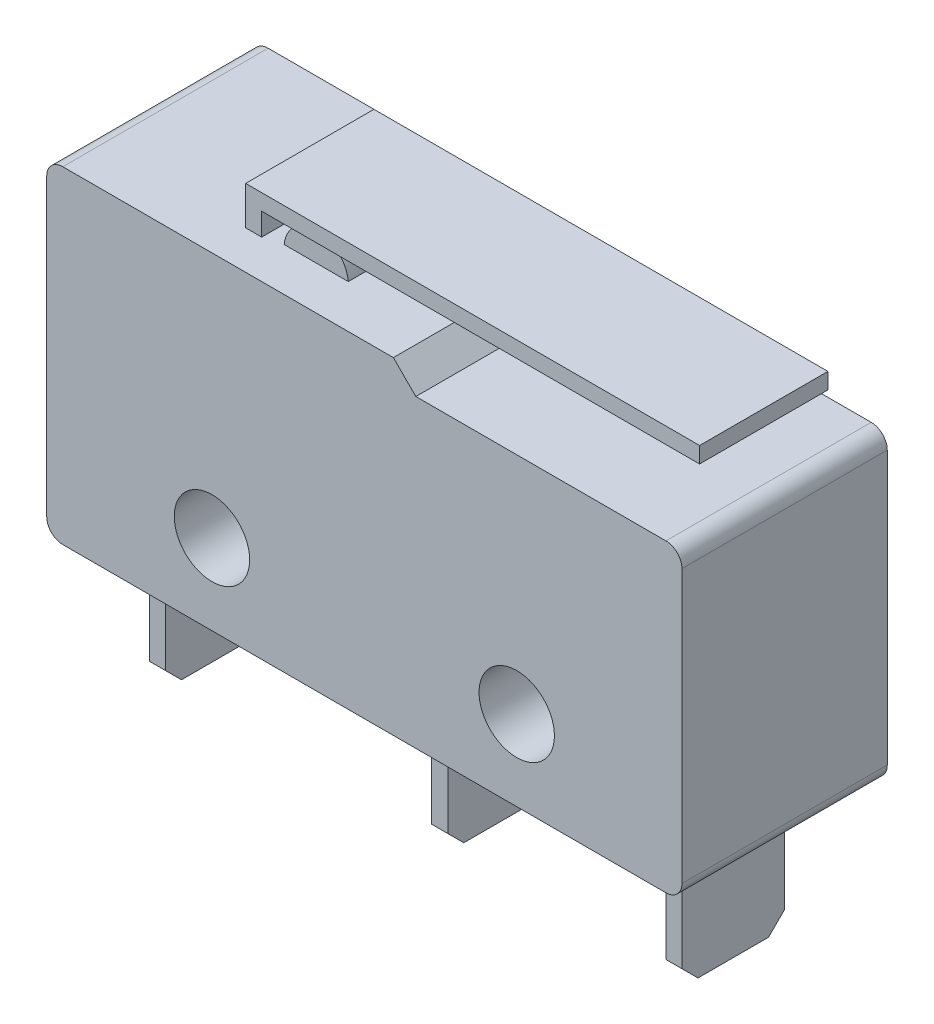
SolidWorks part; units mm, degrees
ref_plane "前视基准面" through (0, 0, 0) normal (0, 0, 1) x (1, 0, 0)
ref_plane "上视基准面" through (0, 0, 0) normal (0, 1, 0) x (1, 0, 0)
ref_plane "右视基准面" through (0, 0, 0) normal (1, 0, 0) x (0, 0, -1)
other "Configuration Table"
sketch "草图1" plane through (0, 0, 0) normal (0, 0, 1) x (1, 0, 0)
  line L1 (9.9, 5.1) -> (-9.9, 5.1)
  line L2 (9.9, 5.1) -> (9.9, -5.1)
  line L3 (9.9, -5.1) -> (-9.9, -5.1)
  line L4 (-9.9, 5.1) -> (-9.9, -5.1)
  line L5 (9.9, 5.1) -> (-9.9, -5.1) construction
  line L6 (9.9, -5.1) -> (-9.9, 5.1) construction
  point P0 (0, 0)
  dimension "D1" = 10.2
  dimension "D2" = 19.8
extrude "凸台-拉伸1" add sketch "草图1" along normal blind 6.4
sketch "草图2" plane through (0, 0, 6.4) normal (0, 0, 1) x (1, 0, 0)
  line L0 (0.0073, 5.998) -> (1.6053, 4.4)
  line L1 (1.6053, 4.4) -> (11.594, 4.4)
  line L2 (11.594, 4.4) -> (11.594, 6.8418)
  line L3 (11.594, 6.8418) -> (0.0073, 6.9858)
  line L4 (0.0073, 6.9858) -> (0.0073, 6.1215)
  line L5 (-9.9, -5.1) -> (9.9, -5.1) construction
  line L6 (9.9, 5.1) -> (-9.9, 5.1) construction
  dimension "D1" = 9.5
  dimension "D2" = 45
extrude "切除-拉伸1" cut sketch "草图2" against normal through all and the other way through all
sketch "草图3" plane through (0, 0, 6.4) normal (0, 0, 1) x (1, 0, 0)
  line L0 (0, 0) -> (0, -5.1) construction
  line L1 (-9.9, -5.1) -> (9.9, -5.1) construction
  line L2 (4.75, -2.6) -> (-4.75, -2.6) construction
  circle A0 centre (-4.75, -2.6) radius 1.175
  circle A1 centre (4.75, -2.6) radius 1.175
  point P12 (0, -2.6)
  dimension "D3" = 2.35
  dimension "D1" = 9.5
  dimension "D4" = 2.5
extrude "切除-拉伸2" cut sketch "草图3" against normal through all
sketch "草图4" plane through (0, 5.1, 0) normal (0, 1, 0) x (1, 0, 0)
  line L0 (-9.9, -3.2) -> (-2.85, -3.2) construction
  line L1 (-9.9, -6.4) -> (-9.9, 0) construction
  line L2 (3.575, -6.4) -> (5.925, -6.4) construction
  line L3 (3.575, -6.4) -> (5.925, -6.4)
  line L4 (4.75, -6.4) -> (4.75, -3.2) construction
  line L6 (-3.85, -1.35) -> (-1.85, -1.35)
  line L7 (-3.85, -1.35) -> (-3.85, -5.05)
  line L8 (-3.85, -5.05) -> (-1.85, -5.05)
  line L9 (-1.85, -1.35) -> (-1.85, -5.05)
  line L10 (-3.85, -1.35) -> (-1.85, -5.05) construction
  line L11 (-3.85, -5.05) -> (-1.85, -1.35) construction
  dimension "D2" = 2
  dimension "D1" = 7.6
  dimension "D3" = 3.7
extrude "凸台-拉伸2" add sketch "草图4" along normal offset from surface (0.9 mm away) 11.1 contours L9 L6 L7 L8 up to face at (0, -5.1, 3.2)
fillet "圆角2" radius 0.5 4 edges at (9.9, 4.4, 3.2) (9.9, -5.1, 3.2) (-9.9, -5.1, 3.2) (-9.9, 5.1, 3.2)
fillet "圆角3" radius 1 2 edges at (-1.85, 6, 3.2) (-3.85, 6, 3.2)
sketch "草图6" plane through (0, -5.1, 0) normal (0, -1, 0) x (1, 0, 0)
  line L0 (-9.9, 3.2) -> (9.9, 3.2) construction
  line L1 (-9.9, 0) -> (-9.9, 6.4) construction
  line L2 (9.9, 6.4) -> (9.9, 0) construction
  line L4 (-8.3, 4.8) -> (-7.8, 4.8)
  line L5 (-8.3, 4.8) -> (-8.3, 1.6)
  line L6 (-8.3, 1.6) -> (-7.8, 1.6)
  line L7 (-7.8, 4.8) -> (-7.8, 1.6)
  line L8 (-8.3, 4.8) -> (-7.8, 1.6) construction
  line L9 (-8.3, 1.6) -> (-7.8, 4.8) construction
  line L10 (0.5, 4.8) -> (1, 4.8)
  line L11 (0.5, 4.8) -> (0.5, 1.6)
  line L12 (0.5, 1.6) -> (1, 1.6)
  line L13 (1, 4.8) -> (1, 1.6)
  line L14 (0.5, 4.8) -> (1, 1.6) construction
  line L15 (0.5, 1.6) -> (1, 4.8) construction
  line L16 (7.8, 4.8) -> (8.3, 4.8)
  line L17 (7.8, 4.8) -> (7.8, 1.6)
  line L18 (7.8, 1.6) -> (8.3, 1.6)
  line L19 (8.3, 4.8) -> (8.3, 1.6)
  line L20 (7.8, 4.8) -> (8.3, 1.6) construction
  line L21 (7.8, 1.6) -> (8.3, 4.8) construction
  point P6 (-8.05, 3.2)
  point P11 (0.75, 3.2)
  point P16 (8.05, 3.2)
  dimension "D1" = 0.5
  dimension "D2" = 3.2
  dimension "D3" = 1.85
  dimension "D4" = 8.8
  dimension "D5" = 7.3
extrude "凸台-拉伸3" add sketch "草图6" along normal blind 3.9
chamfer "倒角1" distance 0.5 angle 45 6 edges at (8.05, -9, 1.6) (8.05, -9, 4.8) (0.75, -9, 4.8) (0.75, -9, 1.6) (-8.05, -9, 1.6) (-8.05, -9, 4.8)
ref_plane "基准面1" through (0, 0, 3.2) normal (0, 0, -1) x (-1, 0, 0)
sketch "草图7" plane through (0, 0, 3.2) normal (0, 0, -1) x (-1, 0, 0)
  line L0 (4.9, 5.1) -> (4.9, 6.3)
  line L1 (-0.9053, 5.1) -> (9.4, 5.1) construction
  line L2 (4.9, 6.3) -> (-9.25, 6.3)
  line L3 (-4.75, -2.6) -> (-0.9342, -2.6) construction
  line L4 (4.75, -2.6) -> (4.75, 0.5974) construction
  line L5 (9.9, 4.6) -> (9.9, -4.6) construction
  line L6 (4.4, 5.1) -> (4.4, 5.8)
  line L7 (4.4, 5.8) -> (-9.25, 5.8)
  line L8 (-9.25, 6.3) -> (-9.25, 5.8)
  line L9 (4.4, 5.1) -> (4.9, 5.1)
  dimension "D1" = 8.9
  dimension "D2" = 14
  dimension "D3" = 5
  dimension "D4" = 0.5
extrude "凸台-拉伸4" add sketch "草图7" along normal mid plane 4
